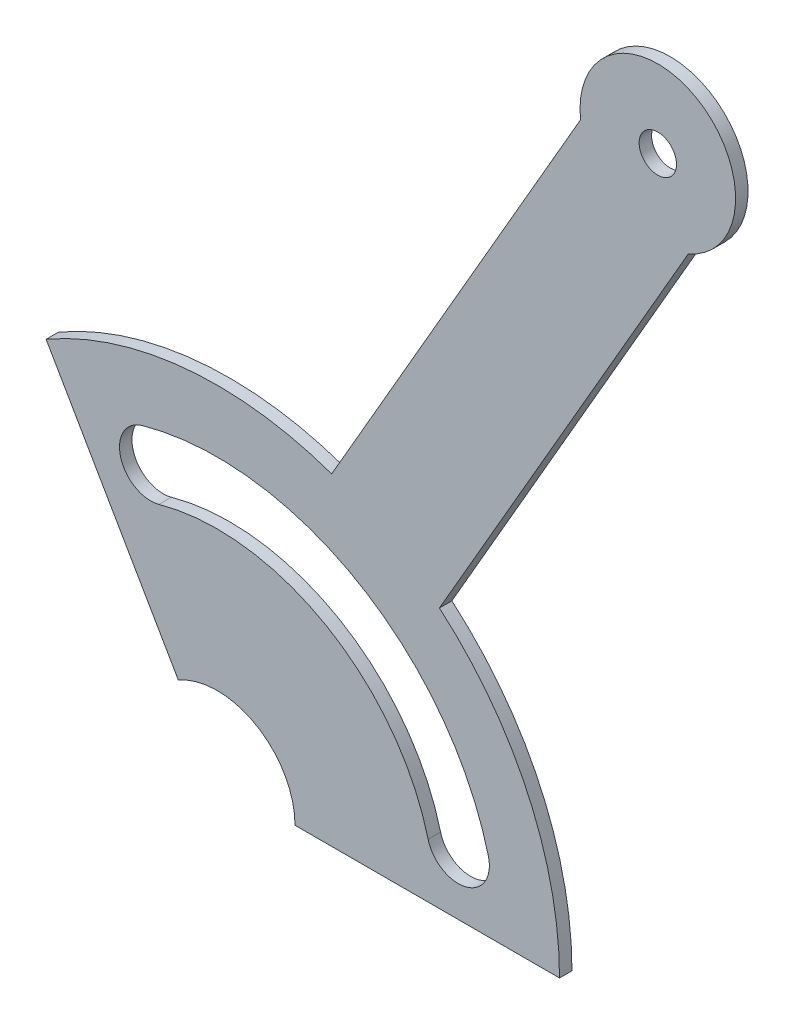
SolidWorks part; units mm, degrees
ref_plane "Front Plane" through (0, 0, 0) normal (0, 0, 1) x (1, 0, 0)
ref_plane "Top Plane" through (0, 0, 0) normal (0, 1, 0) x (1, 0, 0)
ref_plane "Right Plane" through (0, 0, 0) normal (1, 0, 0) x (0, 0, -1)
sketch "Sketch1" plane through (0, 0, 0) normal (0, 0, 1) x (1, 0, 0)
  line L0 (12.5, 0) -> (55, 0)
  line L1 (-6.25, 10.8253) -> (-27.5, 47.6314)
  line L2 (-6.25, 10.8253) -> (0, 0) construction
  line L3 (0, 0) -> (70.7916, 122.6147) construction
  line L4 (35.7019, 41.8375) -> (75.7019, 111.1195)
  line L5 (18.3814, 51.8375) -> (58.3814, 121.1195)
  line L6 (36.0315, 42.4085) -> (79.4519, 117.6147) construction
  line L7 (18.711, 52.4085) -> (62.1314, 127.6147) construction
  line L8 (27.3713, 47.4085) -> (70.7916, 122.6147) construction
  arc A0 (12.5, 0) -> (-6.25, 10.8253) centre (0, 0) ccw
  arc A1 (55, 0) -> (35.7019, 41.8375) centre (0, 0) ccw
  arc A2 (75.7019, 111.1195) -> (58.3814, 121.1195) centre (70.7916, 122.6147) ccw
  arc A3 (18.3814, 51.8375) -> (-27.5, 47.6314) centre (0, 0) ccw
  dimension "D2" = 12.5
  dimension "D3" = 55
  dimension "D6" = 25
  dimension "D1" = 120
  dimension "D7" = 60
  dimension "D8" = 80
  dimension "D4" = 10
  dimension "D5" = 10
base flange "Base-Flange1" sketch "Sketch1" thickness 2 reverse thickness direction no parameters "D1"=0.5
sketch "Sketch6" plane through (0, 0, -2) normal (0, 0, -1) x (-1, 0, 0)
  line L0 (27.5, 47.6314) -> (6.25, 10.8253) construction
  line L1 (-12.5, 0) -> (-55, 0) construction
  arc A0 (-38.7298, 10) -> (10.7047, 38.541) centre (0, 0) cw construction
  arc A1 (12.0427, 43.3586) -> (-43.5711, 11.25) centre (0, 0) ccw
  arc A2 (9.3666, 33.7234) -> (-33.8886, 8.75) centre (0, 0) ccw
  arc A3 (9.3666, 33.7234) -> (12.0427, 43.3586) centre (10.7047, 38.541) ccw
  arc A4 (-43.5711, 11.25) -> (-33.8886, 8.75) centre (-38.7298, 10) ccw
  arc A5 (27.5, 47.6314) -> (-18.3814, 51.8375) centre (0, 0) ccw construction
  point P4 (-20, 34.641)
  dimension "D1" = 10
  dimension "D2" = 10
  dimension "D3" = 10
  dimension "D4" = 10
extrude "Cut-Extrude1" cut sketch "Sketch6" against normal blind 10 normal cut yes
sketch "Sketch9" plane through (0, 0, -2) normal (0, 0, -1) x (-1, 0, 0)
  circle A0 centre (-70.7916, 122.6147) radius 3
  dimension "D1" = 6
extrude "Cut-Extrude2" cut sketch "Sketch9" against normal blind 10 normal cut yes
sketch "Bend-Lines1" plane through (0, 0, 0) normal (0, 1, 0) x (1, 0, 0)
sketch "Bounding-Box1" plane through (0, 0, 0) normal (0, 1, 0) x (1, 0, 0)
sheet metal parameters "Sheet-Metal(1)" thickness 2 parameters "D1"=0.5
flat pattern "Flat-Pattern(1)" [suppressed]
sketch "Bend-Lines2" plane through (0, 0, 0) normal (0, 1, 0) x (1, 0, 0)
sketch "Bounding-Box2" [suppressed] plane through (0, 0, 0) normal (0, 1, 0) x (1, 0, 0)
sheet metal parameters "Sheet-Metal(2)" thickness 2 parameters "D1"=0.5
flat pattern "Flat-Pattern(1)"
sketch "Bend-Lines3" plane through (0, 0, 0) normal (0, 1, 0) x (1, 0, 0)
sketch "Bounding-Box3" [suppressed] plane through (0, 0, 0) normal (0, 1, 0) x (1, 0, 0)
sheet metal parameters "Sheet-Metal(3)" thickness 2 parameters "D1"=0.5
flat pattern "Flat-Pattern(1)"
sketch "Bend-Lines4" plane through (0, 0, 0) normal (0, 1, 0) x (1, 0, 0)
sketch "Bounding-Box4" [suppressed] plane through (0, 0, 0) normal (0, 1, 0) x (1, 0, 0)
